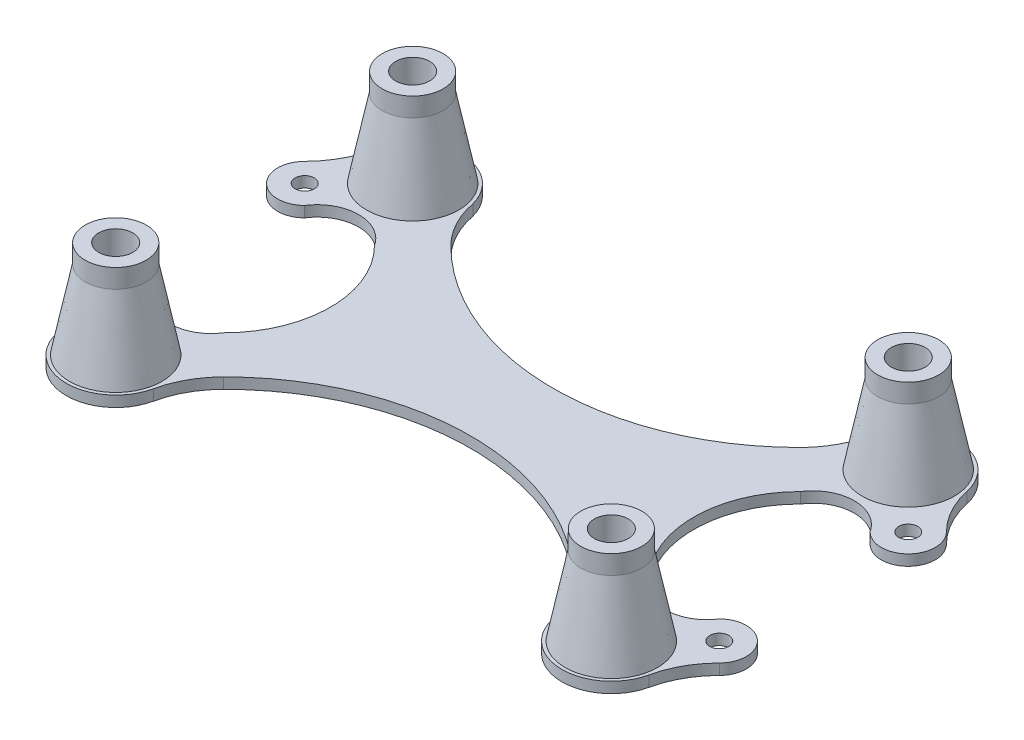
SolidWorks part; units mm, degrees
material "ABS"
ref_plane "Front Plane" through (0, 0, 0) normal (0, 0, 1) x (1, 0, 0)
ref_plane "Top Plane" through (0, 0, 0) normal (0, 1, 0) x (1, 0, 0)
ref_plane "Right Plane" through (0, 0, 0) normal (1, 0, 0) x (0, 0, -1)
sketch "Sketch1" plane through (0, 0, 0) normal (0, 1, 0) x (1, 0, 0)
  line L0 (-17.1901, 8.2099) -> (-8.2099, 17.1901) construction
  line L1 (-12.7, -12.7) -> (12.7, -12.7) construction
  line L2 (-12.7, -12.7) -> (-12.7, 12.7) construction
  line L3 (-12.7, 12.7) -> (12.7, 12.7) construction
  line L4 (12.7, -12.7) -> (12.7, 12.7) construction
  line L5 (-12.7, -12.7) -> (12.7, 12.7) construction
  line L6 (-12.7, 12.7) -> (12.7, -12.7) construction
  line L7 (8.2099, 17.1901) -> (17.1901, 8.2099) construction
  line L8 (-17.1901, -8.2099) -> (-8.2099, -17.1901) construction
  line L9 (8.2099, -17.1901) -> (17.1901, -8.2099) construction
  line L10 (99.3959, 8.2099) -> (108.3761, 17.1901) construction
  line L11 (103.886, -12.7) -> (129.286, -12.7) construction
  line L12 (103.886, -12.7) -> (103.886, 12.7) construction
  line L13 (103.886, 12.7) -> (129.286, 12.7) construction
  line L14 (129.286, -12.7) -> (129.286, 12.7) construction
  line L15 (103.886, -12.7) -> (129.286, 12.7) construction
  line L16 (103.886, 12.7) -> (129.286, -12.7) construction
  line L17 (124.7959, 17.1901) -> (133.7761, 8.2099) construction
  line L18 (99.3959, -8.2099) -> (108.3761, -17.1901) construction
  line L19 (124.7959, -17.1901) -> (133.7761, -8.2099) construction
  line L20 (-17.1901, -61.6401) -> (-8.2099, -52.6599) construction
  line L21 (-12.7, -82.55) -> (12.7, -82.55) construction
  line L22 (-12.7, -82.55) -> (-12.7, -57.15) construction
  line L23 (-12.7, -57.15) -> (12.7, -57.15) construction
  line L24 (12.7, -82.55) -> (12.7, -57.15) construction
  line L25 (-12.7, -82.55) -> (12.7, -57.15) construction
  line L26 (-12.7, -57.15) -> (12.7, -82.55) construction
  line L27 (8.2099, -52.6599) -> (17.1901, -61.6401) construction
  line L28 (-17.1901, -78.0599) -> (-8.2099, -87.0401) construction
  line L29 (8.2099, -87.0401) -> (17.1901, -78.0599) construction
  line L30 (99.3959, -61.6401) -> (108.3761, -52.6599) construction
  line L31 (103.886, -82.55) -> (129.286, -82.55) construction
  line L32 (103.886, -82.55) -> (103.886, -57.15) construction
  line L33 (103.886, -57.15) -> (129.286, -57.15) construction
  line L34 (129.286, -82.55) -> (129.286, -57.15) construction
  line L35 (103.886, -82.55) -> (129.286, -57.15) construction
  line L36 (103.886, -57.15) -> (129.286, -82.55) construction
  line L37 (124.7959, -52.6599) -> (133.7761, -61.6401) construction
  line L38 (99.3959, -78.0599) -> (108.3761, -87.0401) construction
  line L39 (124.7959, -87.0401) -> (133.7761, -78.0599) construction
  line L40 (12.7, -12.7) -> (103.886, -57.15) construction
  line L41 (12.7, -57.15) -> (103.886, -12.7) construction
  circle A2 centre (12.7, -12.7) radius 6.35
  circle A3 centre (-12.7, -12.7) radius 6.35
  circle A4 centre (0, 0) radius 7.175
  circle A5 centre (0, 0) radius 4
  circle A6 centre (0, -69.85) radius 11.6105
  circle A7 centre (116.586, -69.85) radius 11.6105
  arc A8 (-8.2099, -17.1901) -> (8.2099, -17.1901) centre (0, -22.4506) cw
  circle A9 centre (116.586, 0) radius 11.6105
  circle A12 centre (129.286, -12.7) radius 6.35
  circle A13 centre (103.886, -12.7) radius 6.35
  circle A14 centre (116.586, 0) radius 7.175
  circle A15 centre (116.586, 0) radius 4
  circle A16 centre (0, 0) radius 11.6105
  arc A17 (-17.1901, -8.2099) -> (-11.3418, 2.4833) centre (-32.5204, 7.1204) ccw
  arc A18 (108.3761, -17.1901) -> (124.7959, -17.1901) centre (116.586, -22.4506) cw
  arc A19 (17.1901, -8.2099) -> (11.2299, 2.9483) centre (32.5835, 7.1835) cw
  circle A20 centre (-12.7, -57.15) radius 6.35
  circle A21 centre (12.7, -57.15) radius 6.35
  circle A24 centre (0, -69.85) radius 7.175
  circle A25 centre (0, -69.85) radius 4
  arc A26 (-8.2099, -52.6599) -> (8.2099, -52.6599) centre (0, -47.3994) ccw
  arc A27 (99.3959, -8.2099) -> (105.3561, 2.9483) centre (84.0025, 7.1835) ccw
  arc A28 (133.7761, -8.2099) -> (127.9278, 2.4833) centre (149.1064, 7.1204) cw
  arc A29 (133.7761, -61.6401) -> (127.9278, -72.3333) centre (149.1064, -76.9704) ccw
  circle A30 centre (103.886, -57.15) radius 6.35
  circle A31 centre (129.286, -57.15) radius 6.35
  circle A34 centre (116.586, -69.85) radius 7.175
  circle A35 centre (116.586, -69.85) radius 4
  arc A36 (108.3761, -52.6599) -> (124.7959, -52.6599) centre (116.586, -47.3994) ccw
  arc A37 (99.3959, -61.6401) -> (105.2442, -72.3333) centre (84.0656, -76.9704) cw
  arc A38 (17.1901, -61.6401) -> (11.3418, -72.3333) centre (32.5204, -76.9704) ccw
  arc A39 (-17.1901, -61.6401) -> (-11.3418, -72.3333) centre (-32.5204, -76.9704) cw
  arc A40 (8.2099, -17.1901) -> (8.2099, -52.6599) centre (-9.525, -34.925) cw
  arc A41 (17.1901, -8.2099) -> (99.3959, -8.2099) centre (58.293, 32.893) ccw
  arc A42 (108.3761, -17.1901) -> (108.3761, -52.6599) centre (126.111, -34.925) ccw
  arc A43 (99.3959, -61.6401) -> (17.1901, -61.6401) centre (58.293, -102.743) ccw
  point P0 (0, 0)
  point P16 (-12.7, 12.7)
  point P19 (12.7, 12.7)
  point P22 (-12.7, -12.7)
  point P25 (12.7, -12.7)
  point P29 (116.586, 0)
  point P44 (103.886, 12.7)
  point P47 (129.286, 12.7)
  point P50 (103.886, -12.7)
  point P53 (129.286, -12.7)
  point P57 (0, -69.85)
  point P72 (-12.7, -57.15)
  point P75 (12.7, -57.15)
  point P78 (-12.7, -82.55)
  point P81 (12.7, -82.55)
  point P85 (116.586, -69.85)
  point P100 (103.886, -57.15)
  point P103 (129.286, -57.15)
  point P106 (103.886, -82.55)
  point P109 (129.286, -82.55)
  dimension "D1" = 8
  dimension "D3" = 3.175
  dimension "D5" = 8
  dimension "D6" = 12.7
  dimension "D9" = 8
  dimension "D10" = 12.7
  dimension "D13" = 8
  dimension "D14" = 12.7
  dimension "D15" = 14.35
  dimension "D17" = 14.35
  dimension "D18" = 14.35
  dimension "D19" = 25.0809
  dimension "D20" = 25.0809
  dimension "D21" = 58.1282
  dimension "D22" = 58.1282
  dimension "D23" = 12.7
  dimension "D4" = 25.4
  dimension "D7" = 69.85
  dimension "D8" = 25.4
  dimension "D11" = 116.586
  dimension "D12" = 25.4
  dimension "D16" = 25.4
extrude "Boss-Extrude1" add sketch "Sketch1" along normal blind 2.54 contours A3 A8 | A2 A6 A7 A3 A8 A4 | A2 A8 | A6 | A4 A5 | A5 | A7 | A43 A30 A42 A13 A41 A2 A40 A21 | A20 A26 | A21 A26 A20 A24 | A24 A25 | A21 A26 | A30 A36 | A31 A36 A30 A34 | A31 A36 | A13 A18 | A12 A13 A18 A14 | A34 A35 | A25 | A35 | A14 A15 | A15 | A12 A18 | A16 A19 A4 | A17 A3 A16 | A2 A19 A16 | A27 A9 A14 | A12 A28 A9 | A27 A13 A9 | A30 A37 A7 | A31 A7 A29 | A20 A39 A6 | A38 A21 A6 region at (12.7039, 0, 12.697) region at (58.293, 0, 34.925) region at (12.4175, 0, 4.4713) region at (0, 0, 12.1896) region at (0, 0, 11.2821) region at (103.8821, 0, 12.697) region at (104.1685, 0, 4.4713) region at (12.7039, 0, 57.153) region at (-12.7039, 0, 12.697) region at (-12.4175, 0, 4.4601) region at (105.8215, 0, 3.378) region at (116.586, 0, 12.1896) region at (0, 0, 57.6604) region at (103.8821, 0, 57.153) region at (129.0035, 0, 4.4601) region at (129.2899, 0, 12.697) region at (12.4175, 0, 65.3899) region at (10.4233, 0, 65.5325) region at (-12.7039, 0, 57.153) region at (104.1685, 0, 65.3899) region at (116.586, 0, 57.6604) region at (-12.4175, 0, 65.3899) region at (116.586, 0, 58.5679) region at (129.2899, 0, 57.153) region at (129.0035, 0, 65.3899) region at (-6.9721, 0, 0) region at (0, 0, 0) region at (109.6139, 0, 0) region at (116.586, 0, 0) region at (-6.9721, 0, 69.85) region at (0, 0, 69.85) region at (109.6139, 0, 69.85) region at (116.586, 0, 69.85)
extrude "Boss-Extrude2" add sketch "Sketch1<4>" along normal blind 25.4 contours A4 A5 | A14 A15 | A24 A25 | A34 A35 region at (-6.9721, 0, 0) region at (109.6139, 0, 0) region at (-6.9721, 0, 69.85) region at (109.6139, 0, 69.85)
sketch "Sketch1<4>" plane through (0, 0, 0) normal (0, 1, 0) x (1, 0, 0) same geometry as "Sketch1"
hole_wizard "#8 Clearance Hole2" positions "Sketch6" profile "Sketch7" hole size "#8" standard "ANSI Inch" end condition through all
sketch "Sketch6" plane through (0, 2.54, 0) normal (0, 1, 0) x (1, 0, 0)
  point P6 (129.286, -12.7)
  point P9 (129.286, -57.15)
  point P24 (-12.7, -57.15)
  point P28 (-12.7, -12.7)
  point P37 (0, 0)
  point P38 (0, 0)
  point P39 (0, 0)
  point P40 (0, 0)
  point P41 (0, 0)
  point P42 (0, 0)
  point P43 (0, 0)
  point P44 (0, 0)
  point P45 (0, 0)
sketch "Sketch7" plane through (129.286, 2.54, 12.7) normal (1, 0, 0) x (0, 0, 1)
  line L0 (0, 0) -> (0, 2.54)
  line L1 (0, 2.54) -> (2.2479, 2.54)
  line L2 (2.2479, 2.54) -> (2.2479, 0)
  line L5 (2.2479, 0) -> (0, 0)
  line L11 (0, -6.35) -> (0, 107.95) construction
  dimension "Thru Hole Dia." = 4.4958
  dimension "Thru Hole Depth" = 2.54
sketch "Sketch8" plane through (0, 0, 0) normal (1, 0, 0) x (0, 0, -1)
  line L0 (10.8569, 2.54) -> (7.0469, 21.59)
  line L1 (11.6105, 2.54) -> (2.4833, 2.54) construction
  line L2 (7.0469, 21.59) -> (7.0469, 2.54)
  line L3 (7.0469, 2.54) -> (10.8569, 2.54)
  line L4 (0, 0) -> (0, 30.7064) construction
  dimension "D1" = 19.05
  dimension "D2" = 3.81
revolve "Revolve1" add sketch "Sketch8" angle 360 about L4
sketch "Sketch9" plane through (0, 0, 0) normal (0, 1, 0) x (1, 0, 0)
  line L0 (-8.2742, -34.6778) -> (140.5133, -34.6778) construction
  line L1 (66.1196, -79.6601) -> (66.1196, 9.6453) construction
pattern_linear "LPattern1" count 2 spacing 116.586 along (1, 0, 0) count 2 spacing 69.85 along (0, 0, 1) of "Revolve1"
